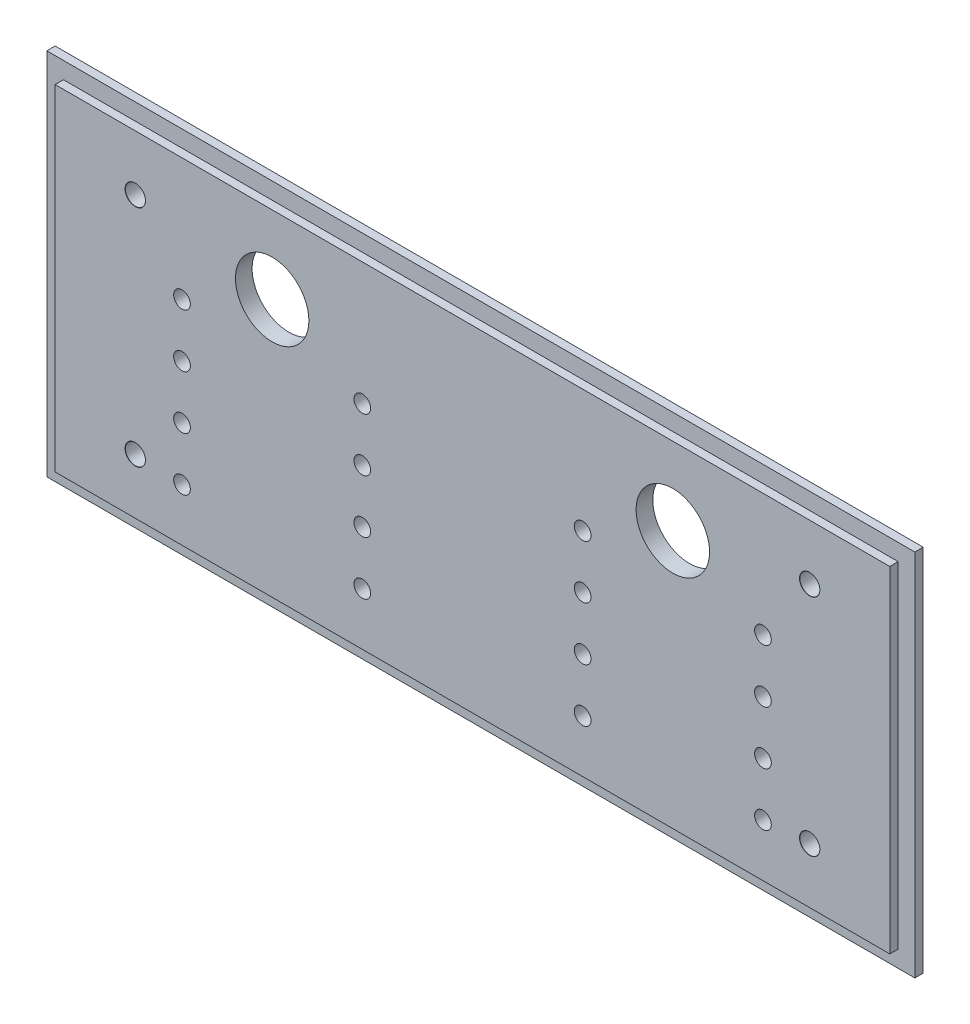
SolidWorks part; units mm, degrees
ref_plane "Plano frontal" through (0, 0, 0) normal (0, 0, 1) x (1, 0, 0)
ref_plane "Plano superior" through (0, 0, 0) normal (0, 1, 0) x (1, 0, 0)
ref_plane "Plano direito" through (0, 0, 0) normal (1, 0, 0) x (0, 0, -1)
sketch "Esboço1" plane through (0, 0, 0) normal (0, 0, 1) x (1, 0, 0)
  line L1 (-63.2916, 33.3513) -> (66.7084, 33.3513)
  line L2 (-63.2916, 33.3513) -> (-63.2916, -21.8987)
  line L3 (-63.2916, -21.8987) -> (66.7084, -21.8987)
  line L4 (66.7084, 33.3513) -> (66.7084, -21.8987)
  dimension "D1" = 130
  dimension "D2" = 55.25
extrude "Ressalto-extrusão1" add sketch "Esboço1" along normal blind 2.5
sketch "Esboço2" plane through (0, 0, 2.5) normal (0, 0, 1) x (1, 0, 0)
  line L0 (1.7084, 33.3513) -> (1.7084, -21.8987) construction
  line L1 (66.7084, 33.3513) -> (-63.2916, 33.3513) construction
  line L2 (-63.2916, -21.8987) -> (66.7084, -21.8987) construction
  line L11 (-54.581, 33.3513) -> (-54.581, -21.8987) construction
  line L13 (-63.2916, 33.3513) -> (66.7084, 33.3513)
  line L14 (-63.2916, 33.3513) -> (-63.2916, -21.8987)
  line L15 (-63.2916, -21.8987) -> (66.7084, -21.8987)
  line L16 (66.7084, 33.3513) -> (66.7084, -21.8987)
  line L17 (-60.7916, 30.8513) -> (64.2084, 30.8513)
  line L18 (-60.7916, 30.8513) -> (-60.7916, -19.3987)
  line L19 (-60.7916, -19.3987) -> (64.2084, -19.3987)
  line L20 (64.2084, 30.8513) -> (64.2084, -19.3987)
  dimension "D1" = 2.5
  dimension "D2" = 2.5
  dimension "D3" = 2.5
  dimension "D4" = 2.5
extrude "Corte-extrusão1" cut sketch "Esboço2" against normal blind 1.25
sketch "Esboço3" plane through (0, 0, 2.5) normal (0, 0, 1) x (1, 0, 0)
  line L0 (-48.7916, 30.8513) -> (-48.7916, -19.3987) construction
  line L1 (64.2084, 30.8513) -> (-60.7916, 30.8513) construction
  line L2 (-60.7916, -19.3987) -> (64.2084, -19.3987) construction
  line L3 (-60.7916, 30.8513) -> (-60.7916, -19.3987) construction
  line L4 (1.7084, 30.8513) -> (1.7084, -19.3987) construction
  line L5 (-60.7916, 5.7263) -> (1.7084, 5.7263) construction
  circle A0 centre (-48.7916, 22.5513) radius 2.75
  circle A1 centre (-48.7916, -11.0987) radius 2.75
  circle A2 centre (52.2084, -11.0987) radius 2.75
  circle A3 centre (52.2084, 22.5513) radius 2.75
  point P14 (-48.7916, 19.8013)
  dimension "D2" = 11.05
  dimension "D1" = 12
hole_wizard "Furos-guia com Ø3.0mm2" positions "Esboço4" profile "Esboço5" hole size "Ø3.0" standard "ISO" end condition through all
sketch "Esboço4" plane through (0, 0, 2.5) normal (0, 0, 1) x (1, 0, 0)
  point P0 (-48.7916, 22.5513)
  point P3 (-48.7916, -11.0987)
  point P6 (52.2084, -11.0987)
  point P9 (52.2084, 22.5513)
sketch "Esboço5" plane through (-48.7916, 22.5513, 2.5) normal (1, 0, 0) x (0, -1, 0)
  line L0 (0, 0) -> (0, 2.5)
  line L1 (0, 2.5) -> (1.5, 2.5)
  line L2 (1.5, 2.5) -> (1.5, 0.025)
  line L3 (1.5, 0.025) -> (1.525, 0)
  line L5 (1.525, 0) -> (0, 0)
  line L6 (-1.5, 0.025) -> (-1.525, 0) construction
  line L11 (0, -6.35) -> (0, 107.95) construction
  dimension "Thru Hole Dia." = 3
  dimension "Thru Hole Depth" = 2.5
  dimension "Near C'Sink Dia." = 3.05
  dimension "Near C'Sink Angle" = 90
sketch "Sketch1" plane through (0, 0, 2.5) normal (0, 0, 1) x (1, 0, 0)
  line L0 (1.7084, 5.7263) -> (-44.2916, 5.7263) construction
  line L1 (-44.2916, 5.7263) -> (-44.2916, 30.7263) construction
  line L2 (-44.2916, 30.7263) -> (-12.2916, 30.7263) construction
  line L3 (-12.2916, 30.7263) -> (-12.2916, -19.2737) construction
  line L4 (-12.2916, -19.2737) -> (-44.2916, -19.2737) construction
  line L5 (-44.2916, -19.2737) -> (-44.2916, 5.7263) construction
  line L6 (-28.2916, 30.7263) -> (-28.2916, -19.2737) construction
  line L7 (-44.2916, 30.7263) -> (-41.7916, 30.7263) construction
  line L8 (-41.7916, 30.7263) -> (-41.7916, -19.2737) construction
  line L11 (1.7084, -19.3987) -> (1.7084, 30.8513) construction
  circle A0 centre (-28.2916, 19.2263) radius 5.5
  circle A1 centre (-41.7916, 12.4763) radius 1.25
  circle A2 centre (-41.7916, 4.4763) radius 1.25
  circle A3 centre (-41.7916, -3.5237) radius 1.25
  circle A4 centre (-41.7916, -11.5237) radius 1.25
  circle A5 centre (-14.7916, 12.4763) radius 1.25
  circle A6 centre (-14.7916, -11.5237) radius 1.25
  circle A7 centre (-14.7916, 4.4763) radius 1.25
  circle A8 centre (-14.7916, -3.5237) radius 1.25
  circle A18 centre (18.2084, -11.5237) radius 1.25
  circle A19 centre (18.2084, -3.5237) radius 1.25
  circle A20 centre (18.2084, 4.4763) radius 1.25
  circle A21 centre (18.2084, 12.4763) radius 1.25
  circle A22 centre (45.2084, -11.5237) radius 1.25
  circle A23 centre (45.2084, -3.5237) radius 1.25
  circle A24 centre (45.2084, 4.4763) radius 1.25
  circle A25 centre (45.2084, 12.4763) radius 1.25
  circle A26 centre (31.7084, 19.2263) radius 5.5
  dimension "D5" = 11
  dimension "D8" = 2.5
  dimension "D1" = 46
  dimension "D2" = 50
  dimension "D3" = 32
  dimension "D4" = 11.5
  dimension "D6" = 2.5
  dimension "D7" = 18.25
  dimension "D10" = 8
  dimension "D9" = 4
extrude "Cut-Extrude1" cut sketch "Sketch1" against normal blind 10
